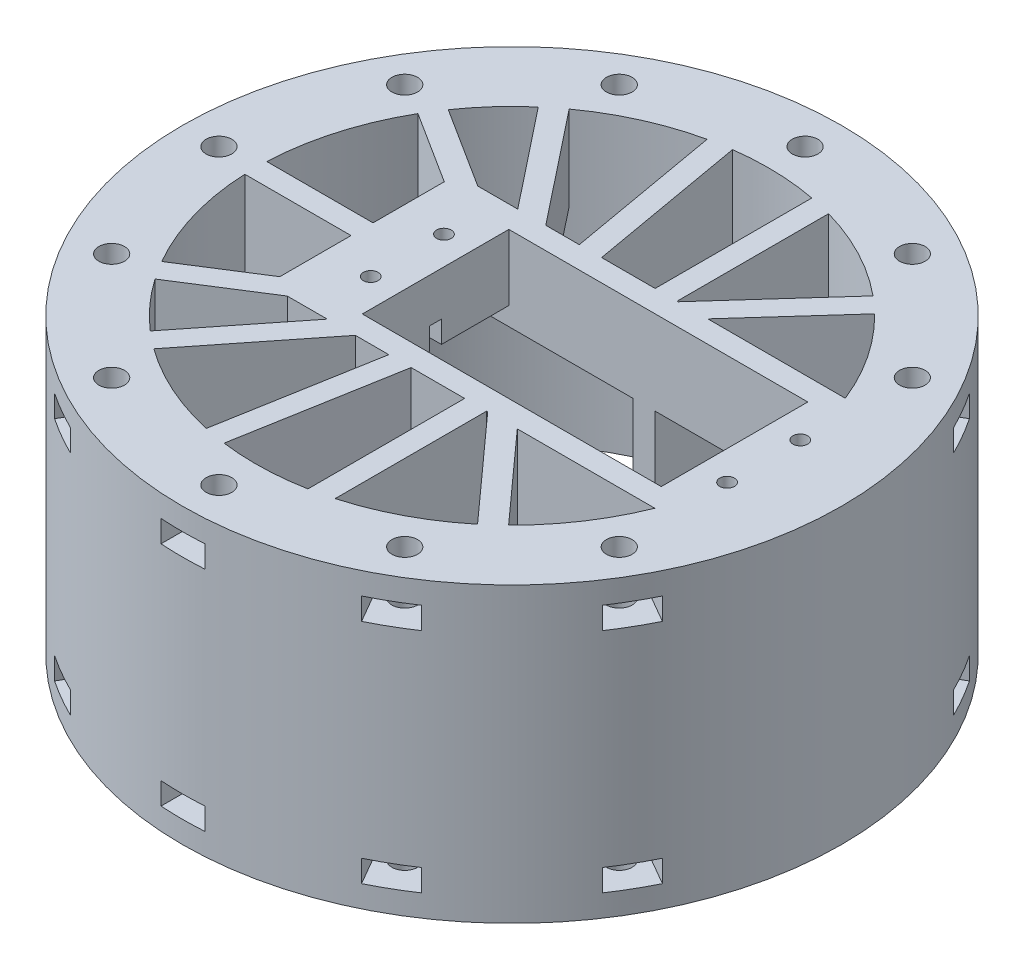
SolidWorks part; units mm, degrees
ref_plane "Front Plane" through (0, 0, 0) normal (0, 0, 1) x (1, 0, 0)
ref_plane "Top Plane" through (0, 0, 0) normal (0, 1, 0) x (1, 0, 0)
ref_plane "Right Plane" through (0, 0, 0) normal (1, 0, 0) x (0, 0, -1)
sketch "Sketch1" plane through (0, 0, 0) normal (0, 1, 0) x (1, 0, 0)
  line L0 (-43.0464, 0) -> (41.9462, 0) construction
  line L1 (0, 43.1152) -> (0, -41.8775) construction
  circle A1 centre (0, 0) radius 45
  dimension "D2" = 90
extrude "Boss-Extrude1" add sketch "Sketch1" along normal blind 40
sketch "Sketch2" plane through (0, 0, 0) normal (0, -1, 0) x (1, 0, 0)
  circle A0 centre (0, 0) radius 35
  dimension "D1" = 70
extrude "Cut-Extrude1" cut sketch "Sketch2" against normal blind 28.5
sketch "Sketch3" plane through (0, 28.5, 0) normal (0, -1, 0) x (1, 0, 0)
  line L0 (35, 0) -> (-35, 0) construction
  line L1 (0, -35) -> (0, 35) construction
  line L3 (37.5324, -10) -> (-17.4676, -10)
  line L4 (37.5324, -10) -> (37.5324, 10)
  line L5 (37.5324, 10) -> (-17.4676, 10)
  line L6 (-17.4676, -10) -> (-17.4676, 10)
  circle A0 centre (0, 0) radius 35 construction
  circle A1 centre (0, 0) radius 35 construction
  dimension "D1" = 20
  dimension "D2" = 55
  dimension "D3" = 10
  dimension "D4" = 37.5324
extrude "Cut-Extrude2" cut sketch "Sketch3" against normal blind 2.5 and the other way up to next
sketch "Sketch4" plane through (0, 31, 0) normal (0, -1, 0) x (1, 0, 0)
  line L0 (37.5324, 0) -> (-17.4676, 0) construction
  line L1 (37.5324, 10) -> (37.5324, -10) construction
  line L2 (-17.4676, 10) -> (-17.4676, -10) construction
  line L3 (0, -10) -> (0, 10) construction
  line L4 (-17.4676, -10) -> (33.541, -10) construction
  line L5 (33.541, 10) -> (-17.4676, 10) construction
  line L7 (30.3722, -10) -> (-10.4278, -10)
  line L8 (30.3722, -10) -> (30.3722, 10)
  line L9 (30.3722, 10) -> (-10.4278, 10)
  line L10 (-10.4278, -10) -> (-10.4278, 10)
  dimension "D1" = 20
  dimension "D2" = 40.8
  dimension "D3" = 30.3722
  dimension "D4" = 10
extrude "Cut-Extrude3" cut sketch "Sketch4" against normal blind 9
sketch "Sketch8" plane through (0, 28.5, 0) normal (0, -1, 0) x (1, 0, 0)
  line L0 (-17.4676, 0) -> (-35, 0) construction
  line L1 (-17.4676, 10) -> (-17.4676, -10) construction
  line L2 (8.0367, 10) -> (8.0367, 34.0648) construction
  line L3 (33.541, 10) -> (-17.4676, 10) construction
  line L4 (8.0367, -10) -> (8.0367, -29.3194) construction
  line L5 (-17.4676, -10) -> (33.541, -10) construction
  line L6 (6.5367, 10) -> (6.5367, 34.3842)
  line L7 (9.5367, 10) -> (9.5367, 33.6757)
  line L8 (9.5367, 10) -> (6.5367, 10)
  line L9 (9.5367, -10) -> (6.5367, -10)
  line L10 (6.5367, -10) -> (6.5367, -34.3842)
  line L11 (9.5367, -10) -> (9.5367, -33.6757)
  line L12 (-17.4676, 1.5) -> (-34.9678, 1.5)
  line L13 (-17.4676, -1.5) -> (-34.9678, -1.5)
  line L14 (-17.4676, 1.5) -> (-17.4676, -1.5)
  arc A0 (33.541, 10) -> (33.541, -10) centre (0, 0) ccw construction
  arc A1 (9.5367, 33.6757) -> (6.5367, 34.3842) centre (7.9531, 33.6757) ccw
  arc A2 (9.5367, -33.6757) -> (6.5367, -34.3842) centre (7.9531, -33.6757) cw
  arc A3 (-34.9678, 1.5) -> (-34.9678, -1.5) centre (-34.9678, 0) ccw
  dimension "D3" = 1.5
  dimension "D1" = 1.5
  dimension "D2" = 1.5
  dimension "D4" = 1.5
extrude "Boss-Extrude2" add sketch "Sketch8" along normal through all
sketch "Sketch16" plane through (0, 31, 0) normal (0, -1, 0) x (1, 0, 0)
  line L0 (-17.4676, 0) -> (37.5324, 0) construction
  line L1 (-17.4676, 10) -> (-17.4676, -10) construction
  line L2 (37.5324, -10) -> (37.5324, 10) construction
  line L3 (30.3722, -0.8) -> (37.5324, -0.8)
  line L4 (-10.4278, -0.8) -> (-17.4676, -0.8)
  line L5 (-10.4278, 10) -> (-10.4278, -10) construction
  line L6 (-10.4278, 0.8) -> (-17.4676, 0.8)
  line L7 (-17.4676, 0.8) -> (-17.4676, -0.8)
  line L8 (-10.4278, 0.8) -> (-10.4278, -0.8)
  line L9 (30.3722, -10) -> (30.3722, 10) construction
  line L10 (30.3722, 0.8) -> (37.5324, 0.8)
  line L11 (37.5324, 0.8) -> (37.5324, -0.8)
  line L12 (30.3722, 0.8) -> (30.3722, -0.8)
  dimension "D1" = 0.8
extrude "Cut-Extrude10" cut sketch "Sketch16" against normal blind 3
sketch "Sketch27" plane through (0, 0, 0) normal (0, -1, 0) x (1, 0, 0)
  line L0 (0, 0) -> (0, -53.17) construction
  line L1 (0, 0) -> (47.7582, -27.5732) construction
  line L3 (31.641, -18.2679) -> (31.641, -21.7321) construction
  line L4 (31.641, -21.7321) -> (34.641, -23.4641) construction
  line L5 (34.641, -23.4641) -> (37.641, -21.7321) construction
  line L6 (37.641, -21.7321) -> (37.641, -18.2679) construction
  line L7 (37.641, -18.2679) -> (34.641, -16.5359) construction
  line L8 (34.641, -16.5359) -> (31.641, -18.2679) construction
  circle A0 centre (0, 0) radius 40 construction
  circle A1 centre (34.641, -20) radius 1.75
  circle A2 centre (0, 0) radius 35 construction
  circle A3 centre (34.641, -20) radius 3 construction
  circle A4 centre (20, -34.641) radius 1.75
  circle A5 centre (0, -40) radius 1.75
  circle A6 centre (-20, -34.641) radius 1.75
  circle A7 centre (-34.641, -20) radius 1.75
  circle A8 centre (-40, 0) radius 1.75
  circle A9 centre (-34.641, 20) radius 1.75
  circle A10 centre (-20, 34.641) radius 1.75
  circle A11 centre (0, 40) radius 1.75
  circle A12 centre (20, 34.641) radius 1.75
  circle A13 centre (34.641, 20) radius 1.75
  circle A15 centre (40, 0) radius 1.75 [skipped]
  point P28 (0, 0)
  point P41 (0, 0)
  dimension "D1" = 80
  dimension "D3" = 3.5
  dimension "D4" = 70
  dimension "D5" = 6
  dimension "D6" = 12
  dimension "D2" = 60
extrude "Cut-Extrude15" cut sketch "Sketch27" against normal through all
ref_plane "Plane1" through (0, 37, 0) normal (0, 1, 0) x (1, 0, 0)
sketch "Sketch28" plane through (0, 37, 0) normal (0, 1, 0) x (1, 0, 0)
  line L0 (0, 0) -> (-54.493, 0) construction
  line L1 (-31.641, 18.2679) -> (-31.641, 21.7321)
  line L2 (-36.5359, 0) -> (-38.2679, 3)
  line L3 (-38.2679, 3) -> (-44.8999, 3)
  line L4 (-31.641, 21.7321) -> (-37.3844, 25.048)
  line L5 (-40.3844, 19.8519) -> (-34.641, 16.5359)
  line L6 (-44.8999, -3) -> (-38.2679, -3)
  line L7 (-38.2679, -3) -> (-36.5359, 0)
  line L8 (-43.4641, 0) -> (-42.5981, -1.5) [skipped]
  line L9 (-41.7321, 3) -> (-42.5981, 1.5) [skipped]
  line L10 (-34.641, 16.5359) -> (-31.641, 18.2679)
  line L11 (-18.2679, 31.641) -> (-16.5359, 34.641)
  line L12 (-16.5359, 34.641) -> (-19.8519, 40.3844)
  line L13 (-25.048, 37.3844) -> (-21.7321, 31.641)
  line L14 (-21.7321, 31.641) -> (-18.2679, 31.641)
  line L15 (0, 36.5359) -> (3, 38.2679)
  line L16 (3, 38.2679) -> (3, 44.8999)
  line L17 (-3, 44.8999) -> (-3, 38.2679)
  line L18 (-3, 38.2679) -> (0, 36.5359)
  line L19 (18.2679, 31.641) -> (21.7321, 31.641)
  line L20 (21.7321, 31.641) -> (25.048, 37.3844)
  line L21 (19.8519, 40.3844) -> (16.5359, 34.641)
  line L22 (16.5359, 34.641) -> (18.2679, 31.641)
  line L23 (31.641, 18.2679) -> (34.641, 16.5359)
  line L24 (34.641, 16.5359) -> (40.3844, 19.8519)
  line L25 (37.3844, 25.048) -> (31.641, 21.7321)
  line L26 (31.641, 21.7321) -> (31.641, 18.2679)
  line L31 (31.641, -18.2679) -> (31.641, -21.7321)
  line L32 (31.641, -21.7321) -> (37.3844, -25.048)
  line L33 (40.3844, -19.8519) -> (34.641, -16.5359)
  line L34 (34.641, -16.5359) -> (31.641, -18.2679)
  line L35 (18.2679, -31.641) -> (16.5359, -34.641)
  line L36 (16.5359, -34.641) -> (19.8519, -40.3844)
  line L37 (25.048, -37.3844) -> (21.7321, -31.641)
  line L38 (21.7321, -31.641) -> (18.2679, -31.641)
  line L39 (0, -36.5359) -> (-3, -38.2679)
  line L40 (-3, -38.2679) -> (-3, -44.8999)
  line L41 (3, -44.8999) -> (3, -38.2679)
  line L42 (3, -38.2679) -> (0, -36.5359)
  line L43 (-18.2679, -31.641) -> (-21.7321, -31.641)
  line L44 (-21.7321, -31.641) -> (-25.048, -37.3844)
  line L45 (-19.8519, -40.3844) -> (-16.5359, -34.641)
  line L46 (-16.5359, -34.641) -> (-18.2679, -31.641)
  line L47 (-31.641, -18.2679) -> (-34.641, -16.5359)
  line L48 (-34.641, -16.5359) -> (-40.3844, -19.8519)
  line L49 (-37.3844, -25.048) -> (-31.641, -21.7321)
  line L50 (-31.641, -21.7321) -> (-31.641, -18.2679)
  line L51 (36.5359, 0) -> (38.2679, -3) [skipped]
  line L52 (38.2679, -3) -> (44.8999, -3) [skipped]
  line L53 (44.8999, 3) -> (38.2679, 3) [skipped]
  line L54 (38.2679, 3) -> (36.5359, 0) [skipped]
  arc A0 (-44.8999, 3) -> (-44.8999, -3) centre (0, 0) ccw
  circle A1 centre (-40, 0) radius 3 construction
  arc A2 (-37.3844, 25.048) -> (-40.3844, 19.8519) centre (0, 0) ccw
  circle A3 centre (-34.641, 20) radius 3 construction
  arc A4 (-19.8519, 40.3844) -> (-25.048, 37.3844) centre (0, 0) ccw
  circle A5 centre (-20, 34.641) radius 3 construction
  arc A6 (3, 44.8999) -> (-3, 44.8999) centre (0, 0) ccw
  circle A7 centre (0, 40) radius 3 construction
  arc A8 (25.048, 37.3844) -> (19.8519, 40.3844) centre (0, 0) ccw
  circle A9 centre (20, 34.641) radius 3 construction
  arc A10 (40.3844, 19.8519) -> (37.3844, 25.048) centre (0, 0) ccw
  circle A11 centre (34.641, 20) radius 3 construction
  arc A14 (37.3844, -25.048) -> (40.3844, -19.8519) centre (0, 0) ccw
  circle A15 centre (34.641, -20) radius 3 construction
  arc A16 (19.8519, -40.3844) -> (25.048, -37.3844) centre (0, 0) ccw
  circle A17 centre (20, -34.641) radius 3 construction
  arc A18 (-3, -44.8999) -> (3, -44.8999) centre (0, 0) ccw
  circle A19 centre (0, -40) radius 3 construction
  arc A20 (-25.048, -37.3844) -> (-19.8519, -40.3844) centre (0, 0) ccw
  circle A21 centre (-20, -34.641) radius 3 construction
  arc A22 (-40.3844, -19.8519) -> (-37.3844, -25.048) centre (0, 0) ccw
  circle A23 centre (-34.641, -20) radius 3 construction
  arc A24 (44.8999, -3) -> (44.8999, 3) centre (0, 0) ccw [skipped]
  circle A25 centre (40, 0) radius 3 construction
  point P94 (0, 0)
  dimension "D1" = 90
  dimension "D2" = 6
  dimension "D3" = 12
extrude "Cut-Extrude17" cut sketch "Sketch28" against normal blind 3
sketch "Sketch29" plane through (0, 28.5, 0) normal (0, -1, 0) x (1, 0, 0)
  line L0 (32.4962, -13) -> (13.7255, -13)
  line L1 (9.5367, -33.6757) -> (9.5367, -10) construction
  line L2 (9.5367, -13) -> (9.5367, -33.6757)
  line L3 (9.5367, -10) -> (33.541, -10) construction
  line L4 (6.5367, -13) -> (-0.7691, -13)
  line L5 (6.5367, -10) -> (6.5367, -34.3842) construction
  line L6 (-20.4676, -11.223) -> (-20.4676, -1.5)
  line L7 (-34.9678, -1.5) -> (-17.4676, -1.5) construction
  line L8 (-20.4676, -1.5) -> (-34.9678, -1.5)
  line L9 (-17.4676, -0.8) -> (-17.4676, -10) construction
  line L10 (32.4962, 13) -> (13.7255, 13)
  line L11 (9.5367, 10) -> (9.5367, 33.6757) construction
  line L12 (9.5367, 13) -> (9.5367, 33.6757)
  line L13 (-7.5493, 34.1761) -> (-3.8154, 13)
  line L14 (6.5367, 13) -> (-0.7691, 13)
  line L15 (6.5367, 34.3842) -> (6.5367, 10) construction
  line L16 (-20.4676, 11.223) -> (-20.4676, 1.5)
  line L17 (-17.4676, 1.5) -> (-34.9678, 1.5) construction
  line L18 (-20.4676, 1.5) -> (-34.9678, 1.5)
  line L19 (6.5367, 13) -> (6.5367, 34.3842)
  line L20 (6.5367, -34.3842) -> (6.5367, -13)
  line L21 (0, 0) -> (-21.7353, -27.4331) construction
  line L22 (-20.5397, -28.3394) -> (-8.3862, -13)
  line L23 (-22.8911, -26.4764) -> (-12.2137, -13)
  line L24 (0, 0) -> (-20.4676, -13) construction
  line L25 (-17.6698, -13) -> (-28.713, -20.0141)
  line L26 (-20.4676, -11.223) -> (-30.3215, -17.4817)
  line L27 (0, 0) -> (-35, 0) construction
  line L28 (-20.4676, 11.223) -> (-30.3215, 17.4817)
  line L29 (-17.6698, 13) -> (-28.713, 20.0141)
  line L30 (-22.8911, 26.4764) -> (-12.2137, 13)
  line L31 (-20.5397, 28.3394) -> (-8.3862, 13)
  line L32 (-12.2137, 13) -> (-17.6698, 13)
  line L33 (0, 0) -> (-6.0777, -34.4683) construction
  line L34 (-4.5949, -34.6971) -> (-0.7691, -13)
  line L35 (-7.5493, -34.1761) -> (-3.8154, -13)
  line L36 (-3.8154, -13) -> (-17.6698, -13)
  line L37 (-4.5949, 34.6971) -> (-0.7691, 13)
  line L38 (-3.8154, 13) -> (-8.3862, 13)
  line L39 (0, 0) -> (23.4214, -26.0084) construction
  line L40 (9.6883, -13) -> (22.2852, -26.9883)
  line L41 (13.7255, -13) -> (24.5145, -24.9808)
  line L42 (13.7255, 13) -> (24.5145, 24.9808)
  line L43 (9.6883, 13) -> (22.2852, 26.9883)
  line L44 (9.6883, -13) -> (9.5367, -13)
  line L45 (9.6883, 13) -> (9.5367, 13)
  arc A0 (9.5367, -33.6757) -> (22.2852, -26.9883) centre (0, 0) ccw
  arc A1 (6.5367, 34.3842) -> (-4.5949, 34.6971) centre (0, 0) ccw
  arc A2 (32.4962, 13) -> (24.5145, 24.9808) centre (0, 0) ccw
  arc A3 (-34.9678, -1.5) -> (-30.3215, -17.4817) centre (0, 0) ccw
  circle A4 centre (0, 0) radius 35 construction
  arc A5 (-7.5493, 34.1761) -> (-20.5397, 28.3394) centre (0, 0) ccw
  arc A6 (-4.5949, -34.6971) -> (6.5367, -34.3842) centre (0, 0) ccw
  arc A7 (-20.5397, -28.3394) -> (-7.5493, -34.1761) centre (0, 0) ccw
  arc A8 (-28.713, -20.0141) -> (-22.8911, -26.4764) centre (0, 0) ccw
  arc A9 (-30.3215, 17.4817) -> (-34.9678, 1.5) centre (0, 0) ccw
  arc A10 (-22.8911, 26.4764) -> (-28.713, 20.0141) centre (0, 0) ccw
  arc A11 (24.5145, -24.9808) -> (32.4962, -13) centre (0, 0) ccw
  arc A12 (22.2852, 26.9883) -> (9.5367, 33.6757) centre (0, 0) ccw
  point P11 (21.5389, -10)
  point P23 (-17.4676, -5.4)
  line M3 (-17.4676, -1.5) -> (-34.9678, -1.5)
  arc M4 (-34.9678, -1.5) -> (6.5367, -34.3842) centre (0, 0) ccw
  line M5 (6.5367, -34.3842) -> (6.5367, -10)
  dimension "D1" = 1.5
  dimension "D2" = 3
  dimension "D3" = 3
  dimension "D4" = 80
  dimension "D5" = 1.5
  dimension "D6" = 1.5
  dimension "D7" = 1.5
sketch "Sketch32" plane through (0, 31, 0) normal (0, -1, 0) x (1, 0, 0)
  line L0 (-17.4676, 0) -> (37.5324, 0) construction
  line L1 (-17.4676, -1.5) -> (-17.4676, 1.5) construction
  line L2 (37.5324, 10) -> (37.5324, -10) construction
  line L3 (10.0324, 0) -> (10.0324, -10) construction
  line L6 (9.5367, -10) -> (33.541, -10) construction
  circle A0 centre (-14.2876, -5) radius 1
  circle A1 centre (-14.2876, 5) radius 1
  circle A2 centre (34.3524, -5) radius 1
  circle A3 centre (34.3524, 5) radius 1
  dimension "D1" = 24.32
  dimension "D3" = 2
  dimension "D2" = 5
extrude "Cut-Extrude21" cut sketch "Sketch32" against normal through all
extrude "Cut-Extrude22" cut sketch "Sketch29" against normal blind 12 contours L28 A9 L18 L16 | L26 L6 M3 M4 | L23 L36 L25 M4 | L35 L36 L22 M4 | L34 L4 M4 M5 | L2 A0 L40 L44 | L41 A11 L0 | L10 A2 L42 | L43 A12 L12 L45 | L19 A1 L37 L14 | L13 A5 L31 L38 | L30 A10 L29 L32 region at (23.89, 28.5, -17.1237) region at (13.9029, 28.5, -24.813) region at (1.8383, 28.5, -24.6789) region at (-27.5459, 28.5, -7.8919) region at (-10.8152, 28.5, -24.1049) region at (-20.9968, 28.5, -18.9781) region at (23.89, 28.5, 17.1237) region at (13.9029, 28.5, 24.813) region at (-10.8152, 28.5, 24.1049) region at (1.8383, 28.5, 24.6789) region at (-27.5459, 28.5, 7.8919) region at (-20.9968, 28.5, 18.9781)
sketch "Sketch33" plane through (0, 0, 1.5) normal (0, 0, 1) x (1, 0, 0)
  line L0 (-17.4676, 14.25) -> (-34.9678, 0)
  line L1 (-17.4676, 0) -> (-17.4676, 28.5) construction
  line L2 (-34.9678, 0) -> (-17.4676, 0)
  line L3 (-17.4676, 0) -> (-34.9678, 0) construction
  line L4 (-17.4676, 0) -> (-17.4676, 14.25)
extrude "Cut-Extrude23" cut sketch "Sketch33" against normal up to next
ref_plane "Plane2" through (0, 3, 0) normal (0, -1, 0) x (-1, 0, 0)
sketch "Sketch34" plane through (0, 3, 0) normal (0, -1, 0) x (-1, 0, 0)
  line L0 (0, 0) -> (0, 45) construction
  line L1 (18.2679, 31.641) -> (21.7321, 31.641)
  line L2 (0, 36.5359) -> (3, 38.2679)
  line L3 (3, 38.2679) -> (3, 44.8999)
  line L4 (21.7321, 31.641) -> (25.048, 37.3844)
  line L5 (19.8519, 40.3844) -> (16.5359, 34.641)
  line L6 (-3, 44.8999) -> (-3, 38.2679)
  line L7 (-3, 38.2679) -> (0, 36.5359)
  line L8 (0, 43.4641) -> (-1.5, 42.5981) [skipped]
  line L9 (3, 41.7321) -> (1.5, 42.5981) [skipped]
  line L10 (16.5359, 34.641) -> (18.2679, 31.641)
  line L11 (31.641, 18.2679) -> (34.641, 16.5359)
  line L12 (34.641, 16.5359) -> (40.3844, 19.8519)
  line L13 (37.3844, 25.048) -> (31.641, 21.7321)
  line L14 (31.641, 21.7321) -> (31.641, 18.2679)
  line L15 (36.5359, 0) -> (38.2679, -3)
  line L16 (38.2679, -3) -> (44.8999, -3)
  line L17 (44.8999, 3) -> (38.2679, 3)
  line L18 (38.2679, 3) -> (36.5359, 0)
  line L19 (31.641, -18.2679) -> (31.641, -21.7321)
  line L20 (31.641, -21.7321) -> (37.3844, -25.048)
  line L21 (40.3844, -19.8519) -> (34.641, -16.5359)
  line L22 (34.641, -16.5359) -> (31.641, -18.2679)
  line L23 (18.2679, -31.641) -> (16.5359, -34.641)
  line L24 (16.5359, -34.641) -> (19.8519, -40.3844)
  line L25 (25.048, -37.3844) -> (21.7321, -31.641)
  line L26 (21.7321, -31.641) -> (18.2679, -31.641)
  line L27 (0, -36.5359) -> (-3, -38.2679)
  line L28 (-3, -38.2679) -> (-3, -44.8999)
  line L29 (3, -44.8999) -> (3, -38.2679)
  line L30 (3, -38.2679) -> (0, -36.5359)
  line L31 (-18.2679, -31.641) -> (-21.7321, -31.641)
  line L32 (-21.7321, -31.641) -> (-25.048, -37.3844)
  line L33 (-19.8519, -40.3844) -> (-16.5359, -34.641)
  line L34 (-16.5359, -34.641) -> (-18.2679, -31.641)
  line L35 (-31.641, -18.2679) -> (-34.641, -16.5359)
  line L36 (-34.641, -16.5359) -> (-40.3844, -19.8519)
  line L37 (-37.3844, -25.048) -> (-31.641, -21.7321)
  line L38 (-31.641, -21.7321) -> (-31.641, -18.2679)
  line L43 (-31.641, 18.2679) -> (-31.641, 21.7321)
  line L44 (-31.641, 21.7321) -> (-37.3844, 25.048)
  line L45 (-40.3844, 19.8519) -> (-34.641, 16.5359)
  line L46 (-34.641, 16.5359) -> (-31.641, 18.2679)
  line L47 (-18.2679, 31.641) -> (-16.5359, 34.641)
  line L48 (-16.5359, 34.641) -> (-19.8519, 40.3844)
  line L49 (-25.048, 37.3844) -> (-21.7321, 31.641)
  line L50 (-21.7321, 31.641) -> (-18.2679, 31.641)
  line L51 (-36.5359, 0) -> (-38.2679, 3) [skipped]
  line L52 (-38.2679, 3) -> (-44.8999, 3) [skipped]
  line L53 (-44.8999, -3) -> (-38.2679, -3) [skipped]
  line L54 (-38.2679, -3) -> (-36.5359, 0) [skipped]
  circle A0 centre (0, 0) radius 45 construction
  circle A1 centre (0, 40) radius 3 construction
  arc A2 (3, 44.8999) -> (-3, 44.8999) centre (0, 0) ccw
  arc A3 (25.048, 37.3844) -> (19.8519, 40.3844) centre (0, 0) ccw
  circle A4 centre (20, 34.641) radius 3 construction
  arc A5 (40.3844, 19.8519) -> (37.3844, 25.048) centre (0, 0) ccw
  circle A6 centre (34.641, 20) radius 3 construction
  arc A7 (44.8999, -3) -> (44.8999, 3) centre (0, 0) ccw
  circle A8 centre (40, 0) radius 3 construction
  arc A9 (37.3844, -25.048) -> (40.3844, -19.8519) centre (0, 0) ccw
  circle A10 centre (34.641, -20) radius 3 construction
  arc A11 (19.8519, -40.3844) -> (25.048, -37.3844) centre (0, 0) ccw
  circle A12 centre (20, -34.641) radius 3 construction
  arc A13 (-3, -44.8999) -> (3, -44.8999) centre (0, 0) ccw
  circle A14 centre (0, -40) radius 3 construction
  arc A15 (-25.048, -37.3844) -> (-19.8519, -40.3844) centre (0, 0) ccw
  circle A16 centre (-20, -34.641) radius 3 construction
  arc A17 (-40.3844, -19.8519) -> (-37.3844, -25.048) centre (0, 0) ccw
  circle A18 centre (-34.641, -20) radius 3 construction
  arc A21 (-37.3844, 25.048) -> (-40.3844, 19.8519) centre (0, 0) ccw
  circle A22 centre (-34.641, 20) radius 3 construction
  arc A23 (-19.8519, 40.3844) -> (-25.048, 37.3844) centre (0, 0) ccw
  circle A24 centre (-20, 34.641) radius 3 construction
  arc A25 (-44.8999, 3) -> (-44.8999, -3) centre (0, 0) ccw [skipped]
  circle A26 centre (-40, 0) radius 3 construction
  point P98 (0, 0)
  dimension "D1" = 6
  dimension "D2" = 90
  dimension "D3" = 12
extrude "Cut-Extrude24" cut sketch "Sketch34" against normal blind 3
